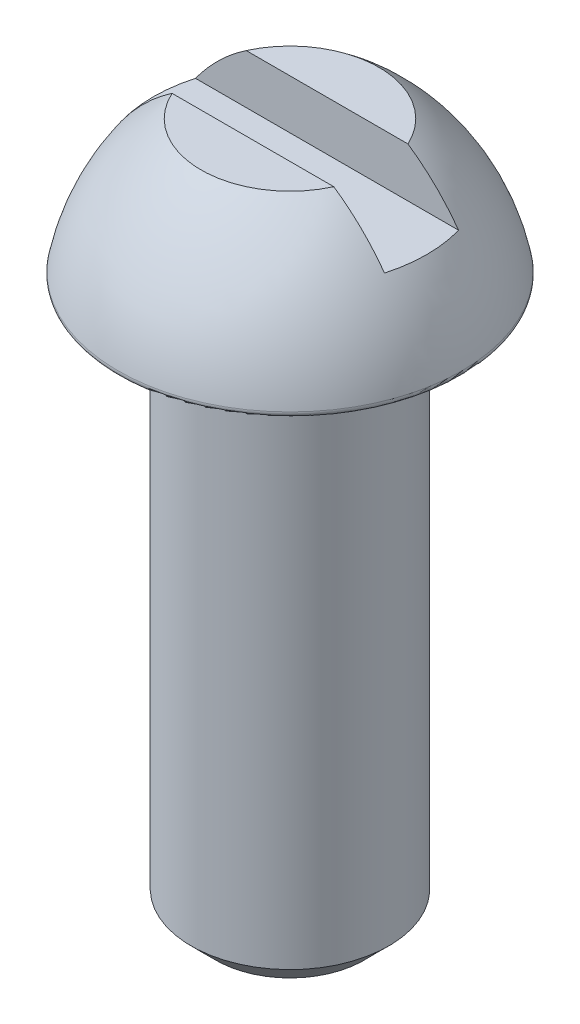
SolidWorks part; units mm, degrees
ref_plane "Спереди" through (0, 0, 0) normal (0, 0, 1) x (1, 0, 0)
ref_plane "Сверху" through (0, 0, 0) normal (0, 1, 0) x (1, 0, 0)
ref_plane "Справа" through (0, 0, 0) normal (1, 0, 0) x (0, 0, -1)
sketch "Эскиз1" plane through (0, 0, 0) normal (0, 0, 1) x (1, 0, 0)
  line L0 (3.5, 11.2) -> (2, 11.2)
  line L1 (0, 0) -> (0, 14)
  line L2 (2, 11.2) -> (2, 0.5)
  line L3 (2, 0.5) -> (1.5, 0)
  line L4 (1.5, 0) -> (0, 0)
  line L5 (0, 14) -> (1.8, 14)
  arc A0 (1.8, 14) -> (3.5, 11.2) centre (-0.8408, 10.4806) cw
  point P9 (0, 0)
  dimension "D2" = 1.8
  dimension "D3" = 4.4
  dimension "D1" = 14
  dimension "D4" = 1.5
  dimension "D5" = 2.8
  dimension "D6" = 3.5
  dimension "D7" = 45
  dimension "D9" = 2
revolve "Повернуть1" add sketch "Эскиз1" angle 360 about L1
fillet "Скругление1" radius 0.1 1 edges at (0, 11.2, -3.5)
sketch "Эскиз3" plane through (0, 14, 0) normal (0, 1, 0) x (-1, 0, 0)
  line L1 (4, -0.75) -> (-4, -0.75)
  line L2 (4, -0.75) -> (4, 0.75)
  line L3 (4, 0.75) -> (-4, 0.75)
  line L4 (-4, -0.75) -> (-4, 0.75)
  dimension "D1" = 1.5
  dimension "D2" = 0.75
  dimension "D3" = 8
  dimension "D4" = 4
extrude "Вырез-Вытянуть2" cut sketch "Эскиз3" against normal blind 1
ref_axis "Ось1" through (0, -104.1565, 0) along (0, 1, 0)
